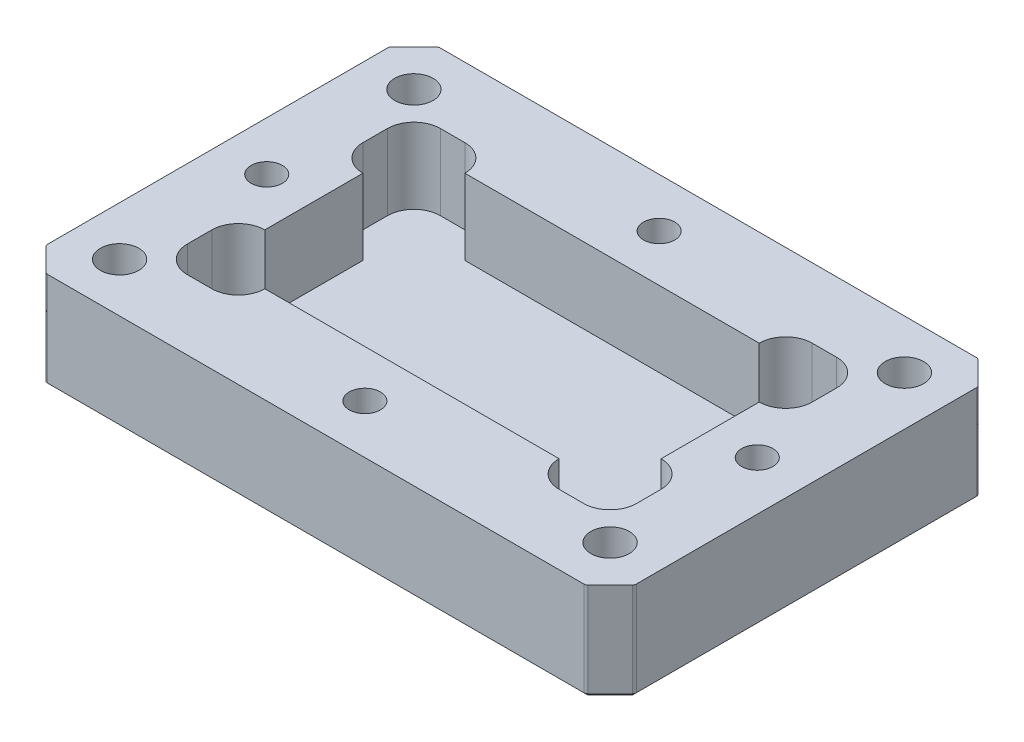
SolidWorks part; units mm, degrees
ref_plane "Front Plane" through (0, 0, 0) normal (0, 0, 1) x (1, 0, 0)
ref_plane "Top Plane" through (0, 0, 0) normal (0, 1, 0) x (1, 0, 0)
ref_plane "Right Plane" through (0, 0, 0) normal (1, 0, 0) x (0, 0, -1)
sketch "Sketch1" plane through (0, 0, 0) normal (0, 1, 0) x (1, 0, 0)
  line L1 (-38.1, 25.4) -> (38.1, 25.4)
  line L2 (-38.1, 25.4) -> (-38.1, -25.4)
  line L3 (-38.1, -25.4) -> (38.1, -25.4)
  line L4 (38.1, 25.4) -> (38.1, -25.4)
  line L5 (-38.1, 25.4) -> (38.1, -25.4) construction
  line L6 (-38.1, -25.4) -> (38.1, 25.4) construction
  point P0 (0, 0)
  dimension "D1" = 76.2
  dimension "D2" = 50.8
extrude "Boss-Extrude1" add sketch "Sketch1" along normal blind 12.7
sketch "Sketch2" plane through (0, 12.7, 0) normal (0, 1, 0) x (1, 0, 0)
  line L1 (-25.654, 12.954) -> (25.654, 12.954)
  line L2 (-25.654, 12.954) -> (-25.654, -12.954)
  line L3 (-25.654, -12.954) -> (25.654, -12.954)
  line L4 (25.654, 12.954) -> (25.654, -12.954)
  line L5 (-25.654, 12.954) -> (25.654, -12.954) construction
  line L6 (-25.654, -12.954) -> (25.654, 12.954) construction
  point P0 (0, 0)
  dimension "D1" = 51.308
  dimension "D2" = 25.908
extrude "Cut-Extrude1" cut sketch "Sketch2" against normal blind 9.779
sketch "Sketch3" plane through (0, 12.7, 0) normal (0, 1, 0) x (1, 0, 0)
  line L0 (25.654, 12.954) -> (-25.654, 12.954) construction
  line L2 (-25.654, 12.954) -> (-25.654, -12.954) construction
  line L3 (-22.479, 16.383) -> (-25.654, 16.383)
  line L4 (-29.083, 12.954) -> (-29.083, 9.779)
  line L6 (-23.2293, 7.3543) -> (-20.0543, 10.5293)
  line L7 (25.654, 12.954) -> (-25.654, 12.954) construction
  arc A0 (-20.0543, 10.5293) -> (-22.479, 16.383) centre (-22.479, 12.954) ccw
  arc A1 (-29.083, 9.779) -> (-23.2293, 7.3543) centre (-25.654, 9.779) ccw
  arc A2 (-25.654, 16.383) -> (-29.083, 12.954) centre (-25.654, 12.954) ccw
  dimension "D1" = 3.429
  dimension "D2" = 3.175
  dimension "D3" = 3.175
extrude "Cut-Extrude2" cut sketch "Sketch3" against normal up to surface (9.779 mm away) up to face at (0, 2.921, 0)
mirror "Mirror1" about plane through (0, 0, 0) normal (0, 0, 1) of "Cut-Extrude2"
mirror "Mirror2" about plane through (0, 0, 0) normal (1, 0, 0) of "Mirror1"
hole_wizard "CBORE for #10 Socket Head Cap Screw" positions "Sketch4" profile "Sketch5" counterbore size "#10" standard "ANSI Inch" end condition through all
sketch "Sketch4" plane through (-13.3951, 0, 69.6344) normal (0, -1, 0) x (1, 0, 0)
  point P0 (-18.3549, -50.5844)
  point P2 (45.1451, -50.5844)
  point P4 (45.1451, -88.6844)
  point P6 (-18.3549, -88.6844)
sketch "Sketch5" plane through (-31.75, 0, 19.05) normal (1, 0, 0) x (0, 0, -1)
  line L0 (0, 0) -> (0, 12.7)
  line L1 (0, 12.7) -> (2.4892, 12.7)
  line L2 (2.4892, 12.7) -> (2.4892, 5.08)
  line L3 (2.4892, 5.08) -> (4.445, 5.08)
  line L4 (4.445, 5.08) -> (4.445, 0)
  line L5 (4.445, 0) -> (0, 0)
  line L6 (0, -6.35) -> (0, 107.95) construction
  dimension "Thru Hole Dia." = 4.9784
  dimension "Thru Hole Depth" = 12.7
  dimension "C'Bore Dia." = 8.89
  dimension "C'Bore Depth" = 5.08
chamfer "Chamfer1" distance 3.175 angle 45 4 edges at (38.1, 6.35, 25.4) (38.1, 6.35, -25.4) (-38.1, 6.35, 25.4) (-38.1, 6.35, -25.4)
fillet "Fillet1" radius 0.508 8 edges at (-38.1, 6.35, -22.225) (-34.925, 6.35, -25.4) (34.925, 6.35, -25.4) (38.1, 6.35, -22.225) (38.1, 6.35, 22.225) (34.925, 6.35, 25.4) (-38.1, 6.35, 22.225) (-34.925, 6.35, 25.4)
chamfer "Chamfer2" distance 0.508 angle 45 16 edges at (36.5125, 0, -23.8125) (38.1, 0, 0) (36.5125, 0, 23.8125) (0, 0, 25.4) (-36.5125, 0, 23.8125) (-38.1, 0, 0) (-36.5125, 0, -23.8125) (0, 0, -25.4) (34.909, 0, 25.3613) (-34.909, 0, 25.3613) (38.0613, 0, 22.209) (-38.0613, 0, 22.209) (38.0613, 0, -22.209) (-38.0613, 0, -22.209) (34.909, 0, -25.3613) (-34.909, 0, -25.3613)
hole_wizard "#10-32 Tapped Hole1" positions "Sketch6" profile "Sketch7" tap size "#10-32" standard "ANSI Inch" end condition through all
sketch "Sketch6" plane through (0, 0, 0) normal (0, -1, 0) x (-1, 0, 0)
  line L0 (0, 19.05) -> (0, -19.05)
  line L3 (31.75, 0) -> (-31.75, 0)
  point P0 (-31.75, 0)
  point P2 (31.75, 0)
  point P4 (0, 19.05)
  point P6 (0, -19.05)
  dimension "D1" = 63.5
  dimension "D2" = 38.1
sketch "Sketch7" plane through (31.75, 0, 0) normal (1, 0, 0) x (0, 0, -1)
  line L0 (0, 0) -> (0, 12.7)
  line L1 (0, 12.7) -> (2.0193, 12.7)
  line L2 (2.0193, 12.7) -> (2.0193, 0)
  line L5 (2.0193, 0) -> (0, 0)
  line L11 (0, -6.35) -> (0, 107.95) construction
  dimension "Thru Tap Drill Dia." = 4.0386
  dimension "Thru Tap Drill Depth" = 12.7
cosmetic thread "Hole Thread1" parameters "D2"=4.826
cosmetic thread "Hole Thread2" parameters "D2"=4.826
cosmetic thread "Hole Thread3" parameters "D2"=4.826
cosmetic thread "Hole Thread4" parameters "D2"=4.826
chamfer "Chamfer3" distance 0.508 angle 45 4 edges at (-31.75, 0, -23.495) (-31.75, 0, 14.605) (31.75, 0, 14.605) (31.75, 0, -23.495)
